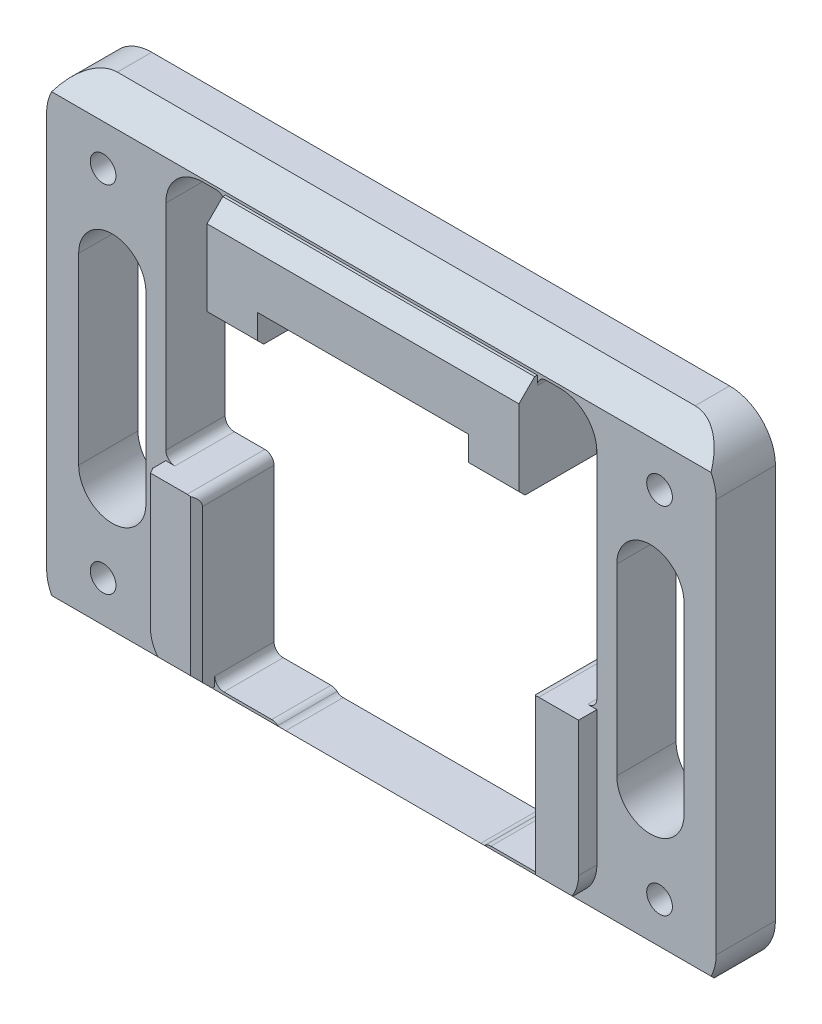
SolidWorks part; units mm, degrees
note: '?' marks a value the reader was unsure of.
material "UHMW PE"
ref_plane "Front Plane" through (0, 0, 0) normal (0, 0, 1) x (1, 0, 0)
ref_plane "Top Plane" through (0, 0, 0) normal (0, 1, 0) x (1, 0, 0)
ref_plane "Right Plane" through (0, 0, 0) normal (1, 0, 0) x (0, 0, -1)
ref_axis "Axis1" through (0, 0, -88.99) along (0, 0, 1)?
ref_axis "Axis2" through (0, -55, 0) along (0, 1, 0)?
ref_axis "Axis3" through (-88.99, 0, 0) along (1, 0, 0)?
sketch "Sketch1" plane through (0, 0, 0) normal (0, 0, 1) x (1, 0, 0)
  line L0 (0, -31.75) -> (0, 0) construction
  line L1 (27.25, -27.25) -> (-27.25, -27.25)
  line L2 (27.25, -27.25) -> (27.25, 27.25)
  line L3 (27.25, 27.25) -> (-27.25, 27.25)
  line L4 (-27.25, -27.25) -> (-27.25, 27.25)
  line L5 (27.25, -27.25) -> (-27.25, 27.25) construction
  line L6 (27.25, 27.25) -> (-27.25, -27.25) construction
  line L7 (-39.75, 47.75) -> (39.75, 47.75)
  line L8 (-39.75, 47.75) -> (-39.75, -31.75)
  line L9 (-39.75, -31.75) -> (39.75, -31.75)
  line L10 (39.75, 47.75) -> (39.75, -31.75)
  point P0 (0, 0)
  dimension "D1" = 54.5
  dimension "D2" = 79.5
  dimension "D3" = 4.5
  dimension "D4" = 79.5
extrude "Boss-Extrude1" add sketch "Sketch1" along normal blind 12.7 contours L10 L7 L8 L9 L1 L4 L3 L2
chamfer "Chamfer2" distance 4 angle 45 4 edges at (39.75, 47.75, 6.35) (39.75, -31.75, 6.35) (-39.75, -31.75, 6.35) (-39.75, 47.75, 6.35)
sketch "Sketch2" plane through (0, 0, 12.7) normal (0, 0, 1) x (1, 0, 0)
  line L0 (0, 0) -> (27.25, 0) construction
  line L1 (27.25, -27.25) -> (27.25, 27.25) construction
  line L2 (0, 0) -> (0, 27.25) construction
  line L3 (27.25, 27.25) -> (-27.25, 27.25) construction
  line L4 (-17.25, 27.25) -> (-17.25, 32.25)
  line L5 (-17.25, 32.25) -> (17.25, 32.25)
  line L6 (17.25, 32.25) -> (17.25, 27.25)
  line L7 (-27.25, -27.25) -> (-27.25, 27.25) construction
  line L8 (-25.5, 27.25) -> (-25.5, 43.25)
  line L9 (27.25, 27.25) -> (-27.25, 27.25) construction
  line L10 (-25.5, 43.25) -> (-29.25, 43.25)
  line L11 (-35.25, 37.25) -> (-35.25, 0.75)
  line L12 (-35.25, 0.75) -> (-27.25, 0.75)
  line L14 (-27.25, -27.25) -> (-27.25, 27.25) construction
  line L15 (-27.25, 0.75) -> (-27.25, 27.25)
  line L16 (-27.25, 27.25) -> (-25.5, 27.25)
  line L17 (27.25, 27.25) -> (25.5, 27.25)
  line L18 (27.25, -27.25) -> (-27.25, -27.25) construction
  line L19 (-17.25, -27.25) -> (17.25, -27.25)
  line L20 (-17.25, -27.25) -> (-17.25, -28)
  line L21 (-17.25, -28) -> (17.25, -28)
  line L22 (17.25, -27.25) -> (17.25, -28)
  line L23 (27.25, 0.75) -> (27.25, 27.25)
  line L25 (35.25, 0.75) -> (27.25, 0.75)
  line L26 (35.25, 37.25) -> (35.25, 0.75)
  line L27 (25.5, 43.25) -> (29.25, 43.25)
  line L28 (25.5, 27.25) -> (25.5, 43.25)
  arc A0 (-29.25, 43.25) -> (-35.25, 37.25) centre (-29.25, 37.25) ccw
  arc A1 (29.25, 43.25) -> (35.25, 37.25) centre (29.25, 37.25) cw
  line M17 (27.25, 27.25) -> (27.25, -27.25)
  line M25 (-27.25, -27.25) -> (-27.25, 27.25)
  line M29 (-27.25, 27.25) -> (27.25, 27.25)
  dimension "D8" = 6
  dimension "D1" = 5
  dimension "D2" = 10
  dimension "D3" = 51
  dimension "D4" = 70.5
  dimension "D5" = 0.75
  dimension "D6" = 28
  dimension "D7" = 70.5
extrude "Cut-Extrude1" cut sketch "Sketch2" against normal through all contours L10 A0 L11 L12 L8 M25 M29 | L6 L5 L4 M29 | A1 L27 L28 L25 L26 M29 M17 | L19 L22 L21 L20
hole_wizard "Tap Drill for  Tap2" [suppressed] positions "Sketch4" profile "Sketch3" hole size "M6x1.0" standard "ANSI Metric"
sketch "Sketch4" plane through (9.5, 47, 0) normal (0, -1, 0) x (0, 0, 1)
  line L0 (6.35, -28.5) -> (6.35, 47.5) construction
  line L4 (0, 9.5) -> (12.7, 9.5) construction
  line L7 (0, -28.5) -> (12.7, -28.5) construction
  line L8 (12.7, 47.5) -> (0, 47.5) construction
  line L9 (0, 43.5) -> (0, -24.5) construction
  line L10 (12.7, 43.5) -> (12.7, -24.5) construction
  point P0 (6.35, 29)
  point P2 (6.35, -10)
  dimension "D1" = 39
sketch "Sketch3" plane through (-19.5, 47, 6.35) normal (1, 0, 0) x (0, 0, 1)
  line L0 (0, 0) -> (0, 16.2618)
  line L1 (0, 16.2618) -> (2.1, 15)
  line L2 (2.1, 15) -> (2.1, 0)
  line L5 (2.1, 0) -> (0, 0)
  line L10 (0, 16.2618) -> (-2.1, 15) construction
  line L11 (0, -6.35) -> (0, 107.95) construction
  dimension "Hole Dia." = 5
  dimension "Hole Depth" = 76
  dimension "Drill Angle" = 118
sketch "Sketch5" plane through (0, 0, 12.7) normal (0, 0, 1) x (1, 0, 0)
  line L1 (47.25, -31.75) -> (-47.25, -31.75)
  line L2 (54.75, -24.25) -> (54.75, 40.25)
  line L3 (47.25, 47.75) -> (-47.25, 47.75)
  line L4 (-54.75, -24.25) -> (-54.75, 40.25)
  line L5 (54.75, -31.75) -> (-54.75, 47.75) construction
  line L6 (54.75, 47.75) -> (-54.75, -31.75) construction
  line L8 (35.75, -31.75) -> (39.75, -27.75)
  line L9 (39.75, -27.75) -> (39.75, 43.75)
  line L10 (39.75, 43.75) -> (35.75, 47.75)
  line L11 (35.75, 47.75) -> (-35.75, 47.75)
  line L12 (-35.75, 47.75) -> (-39.75, 43.75)
  line L13 (-39.75, 43.75) -> (-39.75, -27.75)
  line L14 (-39.75, -27.75) -> (-35.75, -31.75)
  line L15 (-35.75, -31.75) -> (35.75, -31.75)
  line L16 (35.75, -31.75) -> (39.75, -27.75)
  line L17 (39.75, -27.75) -> (39.75, 43.75)
  line L18 (39.75, 43.75) -> (35.75, 47.75)
  line L19 (35.75, 47.75) -> (-35.75, 47.75)
  line L20 (-35.75, 47.75) -> (-39.75, 43.75)
  line L21 (-39.75, 43.75) -> (-39.75, -27.75)
  line L22 (-39.75, -27.75) -> (-35.75, -31.75)
  line L23 (-35.75, -31.75) -> (35.75, -31.75)
  arc A0 (54.75, 40.25) -> (47.25, 47.75) centre (47.25, 40.25) ccw
  arc A1 (47.25, -31.75) -> (54.75, -24.25) centre (47.25, -24.25) ccw
  arc A2 (-47.25, -31.75) -> (-54.75, -24.25) centre (-47.25, -24.25) cw
  arc A3 (-47.25, 47.75) -> (-54.75, 40.25) centre (-47.25, 40.25) ccw
  point P2 (0, 8)
  dimension "D3" = 7.5
  dimension "D2" = 15
  dimension "D1" = 0
extrude "Boss-Extrude2" add sketch "Sketch5" against normal up to surface (12.7 mm away)
sketch "Sketch7" plane through (0, 0, 12.7) normal (0, 0, 1) x (1, 0, 0)
  line L0 (-54.75, 8) -> (0, 8) construction
  line L1 (0, 8) -> (0, 47.75) construction
  line L3 (29.25, -27.25) -> (-29.25, -27.25)
  line L4 (47.25, 47.75) -> (-47.25, 47.75)
  line L5 (-54.75, 40.25) -> (-54.75, -24.25)
  line L6 (-47.25, -31.75) -> (47.25, -31.75)
  line L7 (54.75, -24.25) -> (54.75, 40.25)
  line L8 (47.25, 47.75) -> (-47.25, 47.75)
  line L9 (-54.75, 40.25) -> (-54.75, -24.25)
  line L10 (-47.25, -31.75) -> (47.25, -31.75)
  line L11 (54.75, -24.25) -> (54.75, 40.25)
  line L12 (35.25, -21.25) -> (35.25, 37.25)
  line L13 (29.25, 43.25) -> (-29.25, 43.25)
  line L14 (-35.25, -21.25) -> (-35.25, 37.25)
  line L15 (35.25, -27.25) -> (-35.25, 43.25) construction
  line L16 (35.25, 43.25) -> (-35.25, -27.25) construction
  line L30 (-17.25, -28) -> (17.25, -28)
  line L31 (-17.25, -28) -> (17.25, -28)
  line L32 (-17.25, 32.25) -> (-17.25, 27.25)
  line L33 (-17.25, 32.25) -> (-17.25, 27.25)
  line L34 (-27.25, 0.75) -> (-27.25, -27.25)
  line L35 (17.25, 32.25) -> (-17.25, 32.25)
  line L36 (17.25, 32.25) -> (-17.25, 32.25)
  line L37 (17.25, 27.25) -> (17.25, 32.25)
  line L38 (17.25, 27.25) -> (17.25, 32.25)
  line L39 (-27.25, -27.25) -> (-17.25, -27.25)
  line L40 (-27.25, -27.25) -> (-17.25, -27.25)
  line L41 (-17.25, 27.25) -> (-25.5, 27.25)
  line L42 (-17.25, 27.25) -> (-25.5, 27.25)
  line L43 (25.5, 27.25) -> (17.25, 27.25)
  line L44 (25.5, 27.25) -> (17.25, 27.25)
  line L45 (17.25, -27.25) -> (27.25, -27.25)
  line L46 (27.25, -27.25) -> (27.25, 0.75)
  line L47 (17.25, -27.25) -> (27.25, -27.25)
  line L48 (17.25, -28) -> (17.25, -27.25)
  line L49 (17.25, -28) -> (17.25, -27.25)
  line L50 (-17.25, -27.25) -> (-17.25, -28)
  line L51 (-17.25, -27.25) -> (-17.25, -28)
  line L52 (-35.25, 0.75) -> (-27.25, 0.75)
  line L54 (-35.25, 0.75) -> (-27.25, 0.75)
  line L55 (-35.25, 37.25) -> (-35.25, 0.75)
  line L56 (-27.25, 0.75) -> (-27.25, -27.25)
  line L58 (-35.25, 37.25) -> (-35.25, 0.75)
  line L60 (-25.5, 43.25) -> (-29.25, 43.25)
  line L61 (-25.5, 43.25) -> (-29.25, 43.25)
  line L65 (-25.5, 27.25) -> (-25.5, 43.25)
  line L66 (-25.5, 27.25) -> (-25.5, 43.25)
  line L67 (25.5, 43.25) -> (25.5, 27.25)
  line L68 (27.25, -27.25) -> (27.25, 0.75)
  line L69 (25.5, 43.25) -> (25.5, 27.25)
  line L70 (29.25, 43.25) -> (25.5, 43.25)
  line L71 (29.25, 43.25) -> (25.5, 43.25)
  line L72 (35.25, 0.75) -> (35.25, 37.25)
  line L73 (35.25, 0.75) -> (35.25, 37.25)
  line L74 (27.25, 0.75) -> (35.25, 0.75)
  line L75 (27.25, 0.75) -> (35.25, 0.75)
  arc A0 (-29.25, -27.25) -> (-35.25, -21.25) centre (-29.25, -21.25) cw
  arc A1 (29.25, -27.25) -> (35.25, -21.25) centre (29.25, -21.25) ccw
  arc A2 (35.25, 37.25) -> (29.25, 43.25) centre (29.25, 37.25) ccw
  arc A3 (-29.25, 43.25) -> (-35.25, 37.25) centre (-29.25, 37.25) ccw
  arc A4 (54.75, 40.25) -> (47.25, 47.75) centre (47.25, 40.25) ccw
  arc A5 (-47.25, 47.75) -> (-54.75, 40.25) centre (-47.25, 40.25) ccw
  arc A6 (-54.75, -24.25) -> (-47.25, -31.75) centre (-47.25, -24.25) ccw
  arc A7 (47.25, -31.75) -> (54.75, -24.25) centre (47.25, -24.25) ccw
  arc A8 (54.75, 40.25) -> (47.25, 47.75) centre (47.25, 40.25) ccw
  arc A9 (-47.25, 47.75) -> (-54.75, 40.25) centre (-47.25, 40.25) ccw
  arc A10 (-54.75, -24.25) -> (-47.25, -31.75) centre (-47.25, -24.25) ccw
  arc A11 (47.25, -31.75) -> (54.75, -24.25) centre (47.25, -24.25) ccw
  arc A14 (-29.25, 43.25) -> (-35.25, 37.25) centre (-29.25, 37.25) ccw
  arc A15 (-29.25, 43.25) -> (-35.25, 37.25) centre (-29.25, 37.25) ccw
  arc A16 (35.25, 37.25) -> (29.25, 43.25) centre (29.25, 37.25) ccw
  arc A17 (35.25, 37.25) -> (29.25, 43.25) centre (29.25, 37.25) ccw
  dimension "D3" = 6
  dimension "D4" = 70.5
  dimension "D5" = 70.5
  dimension "D1" = 0
  dimension "D2" = 0
extrude "Cut-Extrude2" cut sketch "Sketch7" against normal blind 3
sketch "Sketch8" plane through (-54.75, 0, 0) normal (-1, 0, 0) x (0, 0, 1)
  line L0 (5.6289, -31.75) -> (12.7, -24.6789)
  line L1 (0, -31.75) -> (9.7, -31.75) construction
  line L2 (12.7, -21.25) -> (12.7, 0.75) construction
  line L3 (12.7, -24.6789) -> (12.7, -31.75)
  line L4 (12.7, -31.75) -> (5.6289, -31.75)
  line L5 (0, 8) -> (9.7, 8) construction
  line L6 (0, 40.25) -> (0, -24.25) construction
  line L7 (12.7, 47.75) -> (5.6289, 47.75)
  line L8 (12.7, 40.6789) -> (12.7, 47.75)
  line L9 (5.6289, 47.75) -> (12.7, 40.6789)
  line L10 (9.7, 40.25) -> (9.7, -24.25) construction
  dimension "D1" = 10
extrude "Cut-Extrude3" cut sketch "Sketch8" against normal through all
chamfer "Chamfer5" distance 0.5 angle 60 2 edges at (-34.9746, -23.0469, 12.7) (-35.25, -10.25, 12.7) first distance on face at (-31.8873, -13.8381, 12.7)
hole_wizard "Tap Drill for M5x0.8 Tap3" positions "Sketch10" profile "Sketch9" hole size "M5x0.8" standard "ANSI Metric" end condition through all
sketch "Sketch10" plane through (0, 0, 9.7) normal (0, 0, 1) x (1, 0, 0)
  line L0 (-54.75, 8) -> (0, 8) construction
  line L1 (-54.75, 40.25) -> (-54.75, -24.25) construction
  line L2 (0, 8) -> (0, 47.75) construction
  line L3 (47.25, 47.75) -> (-47.25, 47.75) construction
  point P0 (-45.5, 37)
  point P24 (-45.5, -21)
  point P25 (45.5, -21)
  point P26 (45.5, 37)
  dimension "D1" = 91
  dimension "D2" = 58
sketch "Sketch9" plane through (-45.5, 37, 9.7) normal (1, 0, 0) x (0, -1, 0)
  line L0 (0, 0) -> (0, 9.7)
  line L1 (0, 9.7) -> (2.1, 9.7)
  line L2 (2.1, 9.7) -> (2.1, 0)
  line L5 (2.1, 0) -> (0, 0)
  line L11 (0, -6.35) -> (0, 107.95) construction
  dimension "Thru Hole Dia." = 4.2
  dimension "Thru Hole Depth" = 9.7
sketch "Sketch11" plane through (0, 0, 9.7) normal (0, 0, 1) x (1, 0, 0)
  line L0 (-44, 23) -> (-44, -7) construction
  line L1 (-38.5, 23) -> (-38.5, -7)
  line L2 (-49.5, 23) -> (-49.5, -7)
  line L3 (0, 0) -> (0, 29.6026) construction
  line L5 (-44, 8) -> (-54.75, 8) construction
  line L6 (-54.75, 40.25) -> (-54.75, -24.25) construction
  line L7 (44, 23) -> (44, -7) construction
  line L8 (38.5, 23) -> (38.5, -7)
  line L9 (49.5, 23) -> (49.5, -7)
  arc A0 (-38.5, 23) -> (-49.5, 23) centre (-44, 23) ccw
  arc A1 (-49.5, -7) -> (-38.5, -7) centre (-44, -7) ccw
  arc A2 (38.5, 23) -> (49.5, 23) centre (44, 23) cw
  arc A3 (49.5, -7) -> (38.5, -7) centre (44, -7) cw
  point P2 (-44, 8)
  point P18 (44, 8)
  dimension "D1" = 5.5
  dimension "D2" = 30
  dimension "D3" = 44
extrude "Cut-Extrude4" cut sketch "Sketch11" against normal through all
sketch "Sketch12" [suppressed] plane through (0, 0, 12.7) normal (0, 0, 1) x (1, 0, 0)
  line L0 (-4.5, 34.5) -> (-14, 34.5)
  line L1 (-3, 36) -> (-3, 41.5)
  line L2 (-4.5, 43) -> (-14, 43)
  line L3 (-15.5, 41.5) -> (-15.5, 36)
  line L4 (-15.5, 30.5) -> (15.5, 30.5) construction
  line L5 (4.5, 43) -> (14, 43)
  line L6 (-15.5, 30.5) -> (15.5, 30.5) construction
  line L8 (34, -28) -> (38, -24)
  line L9 (38, -24) -> (38, 43)
  line L10 (38, 43) -> (34, 47)
  line L11 (34, 47) -> (-34, 47)
  line L12 (-34, 47) -> (-38, 43)
  line L13 (-38, 43) -> (-38, -24)
  line L14 (-38, -24) -> (-34, -28)
  line L15 (-34, -28) -> (34, -28)
  line L16 (34, -28) -> (38, -24)
  line L17 (38, -24) -> (38, 43)
  line L18 (38, 43) -> (34, 47)
  line L19 (34, 47) -> (-34, 47)
  line L20 (-34, 47) -> (-38, 43)
  line L21 (-38, 43) -> (-38, -24)
  line L22 (-38, -24) -> (-34, -28)
  line L23 (-34, -28) -> (34, -28)
  line L25 (0, 30.5) -> (0, 0) construction
  line L26 (3, 36) -> (3, 41.5)
  line L27 (4.5, 34.5) -> (14, 34.5)
  line L28 (15.5, 41.5) -> (15.5, 36)
  line L33 (-24.5, 25.5) -> (-24.5, 45) construction
  arc A0 (-14, 43) -> (-15.5, 41.5) centre (-14, 41.5) ccw
  arc A1 (14, 43) -> (15.5, 41.5) centre (14, 41.5) cw
  arc A2 (3, 41.5) -> (4.5, 43) centre (4.5, 41.5) cw
  arc A3 (4.5, 34.5) -> (3, 36) centre (4.5, 36) cw
  arc A4 (15.5, 36) -> (14, 34.5) centre (14, 36) cw
  arc A7 (-3, 41.5) -> (-4.5, 43) centre (-4.5, 41.5) ccw
  arc A24 (-4.5, 34.5) -> (-3, 36) centre (-4.5, 36) ccw
  arc A25 (-15.5, 36) -> (-14, 34.5) centre (-14, 36) ccw
  point P66 (-3, 43)
  point P69 (-3, 34.5)
  dimension "D6" = 1.5
  dimension "D2" = 1.5
  dimension "D3" = 4
  dimension "D4" = 3
  dimension "D5" = 4
  dimension "D7" = 9
  dimension "D1" = 0
extrude "Cut-Extrude5" [suppressed] cut sketch "Sketch12" against normal through all
sketch "Sketch13" plane through (0, 47.75, 0) normal (0, 1, 0) x (1, 0, 0)
  line L0 (0, 0) -> (0, 20) construction
  line L1 (-47.25, 0) -> (47.25, 0) construction
  circle A0 centre (0, 20) radius 28
  dimension "D1" = 56
  dimension "D2" = 20
extrude "Cut-Extrude6" [suppressed] cut sketch "Sketch13" against normal up to surface (22 mm away)
fillet "Fillet1" radius 1.5 8 edges at (-27.25, 0.75, 6.35) (27.25, 0.75, 6.35) (27.25, -27.25, 4.85) (-27.25, -27.25, 4.85) (-35.25, 0.75, 4.85) (35.25, 0.75, 4.85) (25.5, 43.25, 4.85) (-25.5, 43.25, 4.85)
fillet "Fillet2" radius 1.5 2 edges at (17.25, -28, 4.6895) (-17.25, -28, 4.6895)
fillet "Fillet3" radius 1.5 2 edges at (-17.25, -27.25, 4.85) (17.25, -27.25, 4.85)
chamfer "Chamfer4" distance 1 angle 45 4 edges at (27.25, -12.7145, 12.7) (-27.25, -12.7145, 12.7) (21.375, 27.25, 12.7) (-21.375, 27.25, 12.7) tangent propagation no
hole_wizard "Tap Drill for M5x0.8 Tap2" [suppressed] positions "Sketch15" profile "Sketch14" hole size "M5x0.8" standard "ANSI Metric"
sketch "Sketch15" plane through (0, -28, 0) normal (0, -1, 0) x (-1, 0, 0)
  line L0 (-38, -6.35) -> (38, -6.35) construction
  line L1 (-38, -12.7) -> (-38, 0) construction
  line L2 (38, 0) -> (38, -12.7) construction
  line L4 (0, 0) -> (0, -12.7) construction
  line L5 (34, -12.7) -> (-34, -12.7) construction
  point P2 (-31, -6.35)
  point P21 (31, -6.35)
  dimension "D1" = 62
sketch "Sketch14" plane through (31, -28, 6.35) normal (1, 0, 0) x (0, 0, -1)
  line L0 (0, 0) -> (0, 16.2618)
  line L1 (0, 16.2618) -> (2.1, 15)
  line L2 (2.1, 15) -> (2.1, 0)
  line L5 (2.1, 0) -> (0, 0)
  line L10 (0, 16.2618) -> (-2.1, 15) construction
  line L11 (0, -6.35) -> (0, 107.95) construction
  dimension "Hole Dia." = 4.2
  dimension "Hole Depth" = 30.5
  dimension "Drill Angle" = 118
fillet "Fillet4" [suppressed] radius 1.5
fillet "Fillet5" [suppressed] radius 1.5
